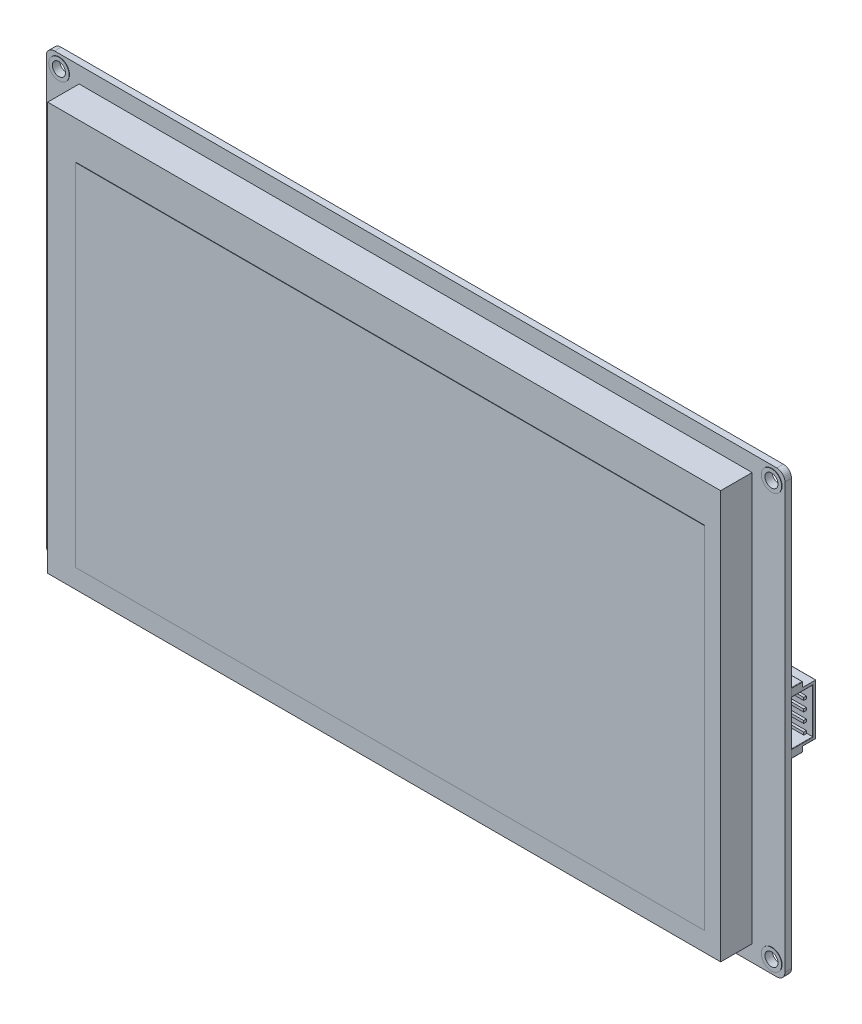
SolidWorks part; units mm, degrees
ref_plane "Ön Düzlem" through (0, 0, 0) normal (0, 0, 1) x (1, 0, 0)
ref_plane "Üst Düzlem" through (0, 0, 0) normal (0, 1, 0) x (1, 0, 0)
ref_plane "Sağ Düzlem" through (0, 0, 0) normal (1, 0, 0) x (0, 0, -1)
sketch "Çizim1" plane through (0, 0, 0) normal (0, 0, 1) x (1, 0, 0)
  line L1 (0, 0) -> (181, 0)
  line L2 (0, 0) -> (0, -108)
  line L3 (0, -108) -> (181, -108)
  line L4 (181, 0) -> (181, -108)
  dimension "D1" = 108
  dimension "D2" = 181
extrude "Yükseklik-Ekstrüzyon1" add sketch "Çizim1" along normal blind 1.6
sketch "Çizim2" plane through (0, 0, 1.6) normal (0, 0, 1) x (1, 0, 0)
  line L0 (0, -3.2) -> (3.2, -3.2)
  line L1 (0, 0) -> (0, -108) construction
  line L2 (181, -3.2) -> (177.8, -3.2)
  line L3 (181, -108) -> (181, 0) construction
  line L4 (3.2, -3.2) -> (3.2, 0)
  line L5 (181, 0) -> (0, 0) construction
  line L6 (177.8, -3.2) -> (177.8, 0)
  line L7 (0, -108) -> (3.2, -108)
  line L8 (0, -108) -> (181, -108) construction
  line L9 (3.2, -108) -> (3.2, -104.8)
  line L10 (181, -108) -> (181, -104.8)
  line L11 (181, -104.8) -> (177.8, -104.8)
  circle A0 centre (3.2, -3.2) radius 1.6
  circle A1 centre (177.8, -3.2) radius 1.6
  circle A2 centre (177.8, -104.8) radius 1.6
  circle A3 centre (3.2, -104.8) radius 1.6
  dimension "D9" = 3.2
  dimension "D10" = 3.2
  dimension "D11" = 3.2
  dimension "D12" = 3.2
  dimension "D1" = 3.2
  dimension "D2" = 3.2
  dimension "D3" = 3.2
  dimension "D4" = 3.2
  dimension "D5" = 3.2
  dimension "D6" = 3.2
  dimension "D7" = 3.2
  dimension "D8" = 3.2
extrude "Kes-Ekstrüzyon1" cut sketch "Çizim2" against normal blind 69.6 contours A3 | A2 | L6 A1 L2 | L2 A1 L6 | L0 A0 L4 | L4 A0 L0 region at (2.5209, -2.5209, 1.6) region at (3.4264, -3.4264, 1.6) region at (177.5736, -3.4264, 1.6) region at (178.4791, -2.5209, 1.6) region at (176.2453, -104.8, 1.6) region at (4.2994, -105.8994, 1.6)
sketch "Çizim3" plane through (0, 0, 1.6) normal (0, 0, 1) x (1, 0, 0)
  circle A0 centre (3.2, -3.2) radius 2.5
  circle A1 centre (177.8, -3.2) radius 2.5
  circle A2 centre (3.2, -104.8) radius 2.5
  circle A3 centre (177.8, -104.8) radius 2.5
  circle A4 centre (3.2, -104.8) radius 1.6 construction
  circle A5 centre (3.2, -3.2) radius 1.6 construction
  circle A6 centre (177.8, -3.2) radius 1.6 construction
  circle A7 centre (177.8, -104.8) radius 1.6 construction
  circle A8 centre (3.2, -104.8) radius 1.6
  circle A9 centre (3.2, -3.2) radius 1.6
  circle A10 centre (177.8, -3.2) radius 1.6
  circle A11 centre (177.8, -104.8) radius 1.6
  dimension "D1" = 5
  dimension "D2" = 5
  dimension "D3" = 5
  dimension "D4" = 5
extrude "Yükseklik-Ekstrüzyon3" add sketch "Çizim3" along normal blind 0.1 and the other way blind 1.7
fillet "Radyus1" radius 2 4 edges at (181, -108, 0.8) (181, 0, 0.8) (0, 0, 0.8) (0, -108, 0.8)
sketch "Çizim4" plane through (0, 0, 1.6) normal (0, 0, 1) x (1, 0, 0)
  line L0 (181, -104) -> (172.95, -104)
  line L1 (181, -106) -> (181, -2) construction
  line L2 (0, -104) -> (8.05, -104)
  line L3 (0, -2) -> (0, -106) construction
  line L4 (172.95, -108) -> (172.95, -104)
  line L5 (2, -108) -> (179, -108) construction
  line L6 (8.05, -104) -> (8.05, -108)
  line L7 (172.95, 0) -> (172.95, -4)
  line L8 (179, 0) -> (2, 0) construction
  line L9 (172.95, -4) -> (181, -4)
  line L10 (0, -4) -> (8.05, -4)
  line L11 (8.05, -4) -> (8.05, 0)
  line L13 (172.95, -4) -> (8.05, -4)
  line L14 (172.95, -4) -> (172.95, -104)
  line L15 (172.95, -104) -> (8.05, -104)
  line L16 (8.05, -4) -> (8.05, -104)
  dimension "D1" = 8.05
  dimension "D2" = 8.05
  dimension "D3" = 4
  dimension "D4" = 4
extrude "Yükseklik-Ekstrüzyon4" add sketch "Çizim4" along normal blind 7.7 contours L13 L16 L15 L14 region at (90.5, -54, 1.6)
sketch "Çizim5" plane through (0, 0, 9.3) normal (0, 0, 1) x (1, 0, 0)
  line L0 (172.95, -104) -> (8.05, -104) construction
  line L1 (169.03, -99.22) -> (14.95, -99.22)
  line L2 (169.03, -99.22) -> (169.03, -13.3)
  line L3 (169.03, -13.3) -> (14.95, -13.3)
  line L4 (14.95, -99.22) -> (14.95, -13.3)
  line L5 (172.95, -4) -> (172.95, -104) construction
  line L6 (8.05, -4) -> (8.05, -104) construction
  line L8 (172.95, -4) -> (8.05, -4) construction
  dimension "D1" = 4.78
  dimension "D2" = 3.92
  dimension "D3" = 6.9
  dimension "D4" = 9.3
extrude "Yükseklik-Ekstrüzyon5" add sketch "Çizim5" along normal blind 0.1
sketch "Çizim6" plane through (0, 0, 9.4) normal (0, 0, 1) x (1, 0, 0)
  line L1 (172.95, -104) -> (8.05, -104)
  line L2 (172.95, -104) -> (172.95, -4)
  line L3 (172.95, -4) -> (8.05, -4)
  line L4 (8.05, -104) -> (8.05, -4)
sketch "Çizim9" plane through (0, 0, 0) normal (0, 0, -1) x (-1, 0, 0)
  line L0 (-181, -54) -> (-171.5405, -54) construction
  line L1 (-181, -106) -> (-181, -2) construction
  line L2 (-181, -61.4) -> (-181, -46.6)
  line L4 (-181, -54) -> (-181, -60.25)
  line L5 (-181, -54) -> (-181, -47.75)
  line L6 (-181, -60.25) -> (-172.8, -60.25)
  line L7 (-181, -47.75) -> (-172.8, -47.75)
  line L8 (-172.8, -60.25) -> (-172.8, -47.75)
  dimension "D2" = 7.4
  dimension "D4" = 6.25
  dimension "D5" = 6.25
  dimension "D6" = 8.2
extrude "Yükseklik-Ekstrüzyon9" add sketch "Çizim9" along normal blind 6 contours L2 L0 L8 L7 | L0 L2 L6 L8 region at (176.9, -50.875, 0) region at (176.9, -57.125, 0)
sketch "Çizim10" plane through (0, 0, 0) normal (0, 0, -1) x (-1, 0, 0)
  line L0 (-181, -54) -> (-181, -61.5)
  line L1 (-181, -47.75) -> (-181, -60.25) construction
  line L2 (-181, -106) -> (-181, -60.25) construction
  line L3 (-181, -54) -> (-181, -46.5)
  line L4 (-181, -47.75) -> (-181, -2) construction
  line L5 (-181, -61.5) -> (-175.75, -61.5)
  line L6 (-175.75, -61.5) -> (-175.75, -60.25)
  line L7 (-181, -60.25) -> (-172.8, -60.25) construction
  line L8 (-181, -46.5) -> (-175.75, -46.5)
  line L9 (-175.75, -46.5) -> (-175.75, -47.75)
  line L10 (-181, -47.75) -> (-172.8, -47.75) construction
  line L11 (-175.75, -60.25) -> (-181, -60.25)
  line L12 (-175.75, -47.75) -> (-181, -47.75)
  line L14 (-175.75, -61.5) -> (-181, -61.5)
  line L15 (-175.75, -61.5) -> (-175.75, -60.25)
  line L16 (-175.75, -60.25) -> (-181, -60.25)
  line L17 (-181, -61.5) -> (-181, -60.25)
  line M9 (-172.8, -60.25) -> (-181, -60.25)
  line M10 (-181, -60.25) -> (-181, -106)
  line M18 (-181, -2) -> (-181, -47.75)
  line M19 (-181, -47.75) -> (-172.8, -47.75)
  dimension "D1" = 7.5
  dimension "D2" = 7.5
  dimension "D3" = 5.25
  dimension "D4" = 1.25
extrude "Yükseklik-Ekstrüzyon10" add sketch "Çizim10" along normal blind 2.75 contours L5 L6 M9 M10 | L9 L8 M18 M19 region at (178.375, -60.875, 0) region at (178.375, -47.125, 0)
sketch "Çizim11" plane through (181, 0, 0) normal (1, 0, 0) x (0, 0, -1)
  line L2 (0, -48.5) -> (5.25, -48.5)
  line L3 (5.25, -48.5) -> (5.25, -59.5)
  line L4 (5.25, -59.5) -> (2, -59.5)
  line L8 (6, -60.25) -> (6, -47.75)
  line L9 (6, -47.75) -> (2.75, -47.75)
  line L10 (2.75, -47.75) -> (2.75, -46.5)
  line L11 (2.75, -46.5) -> (2.75, -47.75) construction
  line L12 (2.75, -46.5) -> (0, -46.5)
  line L13 (0, -46.5) -> (0, -61.5)
  line L14 (0, -61.5) -> (2.75, -61.5)
  line L15 (2.75, -61.5) -> (2.75, -60.25)
  line L16 (2.75, -60.25) -> (6, -60.25)
  line L18 (2, -59.5) -> (0, -59.5)
  dimension "D1" = 0.75
  dimension "D2" = 0.75
  dimension "D7" = 0.75
extrude "Kes-Ekstrüzyon3" cut sketch "Çizim11" against normal blind 11.75 contours L18 L4 L3 L2 L13 region at (181, -54, -2.625)
sketch "Çizim12" plane through (0, 0, -6) normal (0, 0, -1) x (-1, 0, 0)
  line L0 (-181, -47.75) -> (-172.8, -47.75) construction
  line L1 (-172.8, -60.25) -> (-173.3043, -60.25)
  line L2 (-172.8, -60.25) -> (-172.8, -47.75)
  line L3 (-172.8, -47.75) -> (-173.3043, -47.75)
  line L4 (-173.3043, -60.25) -> (-173.3043, -47.75)
extrude "Yükseklik-Ekstrüzyon11" add sketch "Çizim12" against normal up to surface (6 mm away) up to face at (142.11, -54, 0)
sketch "Çizim13" plane through (181, 0, 0) normal (1, 0, 0) x (0, 0, -1)
  line L0 (0, -61.5) -> (0, -46.5)
  line L1 (0, -46.5) -> (2.75, -46.5)
  line L2 (2.75, -46.5) -> (2.75, -47.75)
  line L3 (2.75, -47.75) -> (6, -47.75)
  line L4 (6, -47.75) -> (6, -60.25)
  line L5 (6, -60.25) -> (2.75, -60.25)
  line L6 (2.75, -60.25) -> (2.75, -61.5)
  line L7 (2.75, -61.5) -> (0, -61.5)
  line L9 (5.25, -59.5) -> (0, -59.5)
  line L10 (5.25, -59.5) -> (5.25, -48.5)
  line L11 (5.25, -48.5) -> (0, -48.5)
  line L12 (0, -59.5) -> (0, -48.5)
  line M1 (2.75, -46.5) -> (0, -46.5)
  line M7 (0, -61.5) -> (2.75, -61.5)
  line M8 (2.75, -61.5) -> (2.75, -60.25)
  line M9 (2.75, -60.25) -> (6, -60.25)
  line M10 (6, -60.25) -> (6, -47.75)
  line M11 (6, -47.75) -> (2.75, -47.75)
  line M12 (2.75, -47.75) -> (2.75, -46.5)
  line M13 (5.25, -59.5) -> (0, -59.5)
  line M15 (0, -48.5) -> (5.25, -48.5)
  line M16 (5.25, -48.5) -> (5.25, -59.5)
extrude "Yükseklik-Ekstrüzyon12" add sketch "Çizim13" along normal blind 0.001 contours L0 M7 M8 M9 M10 M11 M12 M1 M15 M16 M13 region at (181, -60.5, -0.1616)
sketch "Çizim14" plane through (173.3043, 0, 0) normal (1, 0, 0) x (0, 0, -1)
  line L1 (3.65, -58) -> (3, -58)
  line L2 (3.65, -58) -> (3.65, -57.35)
  line L3 (3.65, -57.35) -> (3, -57.35)
  line L4 (3, -58) -> (3, -57.35)
  line L5 (3, -58) -> (3, -54.9) construction
  line L6 (3.65, -55.55) -> (3.65, -52.45) construction
  line L7 (3, -54.9) -> (3.65, -54.9)
  line L8 (3, -54.9) -> (3, -55.55)
  line L9 (3, -55.55) -> (3.65, -55.55)
  line L10 (3.65, -54.9) -> (3.65, -55.55)
  line L11 (3, -53.1) -> (3, -50) construction
  line L12 (3.65, -52.45) -> (3, -52.45)
  line L13 (3.65, -52.45) -> (3.65, -53.1)
  line L14 (3.65, -53.1) -> (3, -53.1)
  line L15 (3, -52.45) -> (3, -53.1)
  line L16 (0, -48.5) -> (5.25, -48.5) construction
  line L17 (3, -50) -> (3.65, -50)
  line L18 (3, -50) -> (3, -50.65)
  line L19 (3, -50.65) -> (3.65, -50.65)
  line L20 (3.65, -50) -> (3.65, -50.65)
  line L23 (6, -60.25) -> (6, -47.75) construction
  line L25 (0, -48.5) -> (0, -59.5) construction
  dimension "D1" = 0.65
  dimension "D2" = 0.65
  dimension "D3" = 1.5
  dimension "D4" = 3.1
  dimension "D5" = 0.65
  dimension "D6" = 3.1
  dimension "D7" = 0.65
  dimension "D8" = 3.1
  dimension "D9" = 0.65
  dimension "D10" = 3
  dimension "D11" = 0.65
  dimension "D12" = 3
  dimension "D13" = 2.35
extrude "Yükseklik-Ekstrüzyon13" add sketch "Çizim14" along normal up to surface (7.6967 mm away) up to face at (181.001, -54, -2.7917)
fillet "Radyus2" radius 0.1 23 edges at (181.001, -61.5, -1.375) (181.001, -60.875, -2.75) (181.001, -60.25, -4.375) (181.001, -59.5, -2.625) (175.75, -61.5, -1.375) (178.3755, -61.5, -2.75) (175.75, -60.875, -2.75) (175.75, -60.25, -1.375) (178.3755, -60.25, -2.75) (172.8, -60.25, -3) (176.9005, -60.25, -6) (172.8, -54, -6) (175.75, -46.5, -1.375) (175.75, -47.125, -2.75) (175.75, -47.75, -1.375) (172.8, -47.75, -3) (176.9005, -47.75, -6) (181.001, -54, -5.25) (181.001, -54, -6) (181.001, -48.5, -2.625) (181.001, -46.5, -1.375) (178.3755, -46.5, -2.75) (178.3755, -47.75, -2.75)
